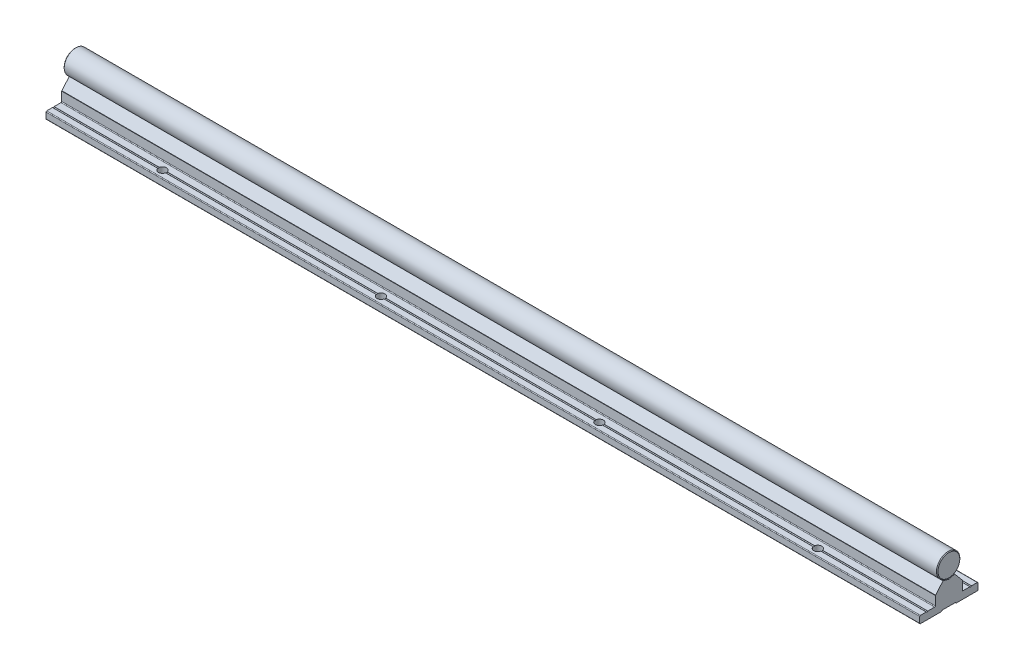
SolidWorks part; units mm, degrees
note: The reader was unsure of these and kept them because the rebuilt part matched: shared geometry of "Эскиз1<3>".
ref_plane "Спереди" through (0, 0, 0) normal (0, 0, 1) x (1, 0, 0)
ref_plane "Сверху" through (0, 0, 0) normal (0, 1, 0) x (1, 0, 0)
ref_plane "Справа" through (0, 0, 0) normal (1, 0, 0) x (0, 0, -1)
sketch "Эскиз1" plane through (0, 0, 0) normal (1, 0, 0) x (0, 0, -1)
  line L0 (0, 0) -> (0, -25) construction
  line L1 (0, -25) -> (-20, -25) construction
  line L2 (-4.75, -25) -> (-20, -25)
  line L3 (-20, -25) -> (-20, -20)
  line L4 (-20, -20) -> (-9.25, -20)
  line L5 (-9.25, -20) -> (-9.25, -13.3)
  line L6 (-9.25, -13.3) -> (-9.1101, -13.3)
  line L7 (-9.1101, -13.3) -> (-4, -7.21)
  line L8 (-4, -7.21) -> (-3.8, -7.21)
  line L9 (-3.8, -7.21) -> (0, -8.3557)
  line L10 (-2.75, -7.5266) -> (-2.75, -19) construction
  line L11 (-2.75, -19) -> (-4.75, -19) construction
  line L12 (-4.75, -19) -> (-4.75, -25) construction
  line L13 (-4.75, -25) -> (-4.75, -24.4)
  line L14 (-4.75, -24.4) -> (4.75, -24.4)
  line L15 (4.75, -25) -> (4.75, -24.4)
  line L16 (4.75, -25) -> (20, -25)
  line L17 (20, -25) -> (20, -20)
  line L18 (20, -20) -> (9.25, -20)
  line L19 (9.25, -20) -> (9.25, -13.3)
  line L20 (9.25, -13.3) -> (9.1101, -13.3)
  line L21 (9.1101, -13.3) -> (4, -7.21)
  line L22 (4, -7.21) -> (3.8, -7.21)
  line L23 (3.8, -7.21) -> (0, -8.3557)
  line L24 (-15, -20) -> (-15, -25) construction
  line L25 (-15.5, -20) -> (-15, -20.5)
  line L26 (-15, -20.5) -> (-14.5, -20)
  line L27 (15.5, -20) -> (15, -20.5)
  line L28 (15, -20) -> (15, -25) construction
  line L29 (15, -20.5) -> (14.5, -20)
  circle A0 centre (0, 0) radius 8
  point P17 (0, -24.4)
  dimension "D1" = 16
  dimension "D2" = 17.79
  dimension "D3" = 8
  dimension "D4" = 40
  dimension "D5" = 0.2
  dimension "D6" = 18.5
  dimension "D7" = 5
  dimension "D8" = 40
  dimension "D9" = 11.7
  dimension "D10" = 4.75
  dimension "D11" = 2.75
  dimension "D12" = 6
  dimension "D13" = 0.6
  dimension "D14" = 1
  dimension "D15" = 15
  dimension "D16" = 25
extrude "Опора" add sketch "Эскиз1" along normal mid plane 3000 contours L27 L29 L18 L19 L20 L21 L22 L23 L9 L8 L7 L6 L5 L4 L26 L25 L3 L2 L13 L14 L15 L16 L17
extrude "Вал" add sketch "Эскиз1<3>" along normal mid plane 3000 separate body contours A0
sketch "Эскиз1<3>" plane through (0, 0, 0) normal (1, 0, 0) x (0, 0, -1) same geometry as "Эскиз1"
fillet "Скругление4" radius 0.2 7 edges at (0, -20, -15.5) (0, -20, -14.5) (0, -20, 14.5) (0, -20, 15.5) (0, -8.3557, 0) (0, -24.4, -4.75) (0, -24.4, 4.75)
sketch "Эскиз2" plane through (0, -20, 0) normal (0, 1, 0) x (1, 0, 0)
  line L0 (-1425, 15) -> (-1425, -15) construction
  line L1 (1500, 15) -> (-1500, 15) construction
  line L2 (1500, -15) -> (-1500, -15) construction
  line L3 (-1500, 8) -> (-1500, -8) construction
  line L4 (-1275, 15) -> (-1275, -15) construction
  line L5 (-1125, 15) -> (-1125, -15) construction
  line L6 (-975, 15) -> (-975, -15) construction
  line L7 (-825, 15) -> (-825, -15) construction
  line L8 (-675, 15) -> (-675, -15) construction
  line L9 (-525, 15) -> (-525, -15) construction
  line L10 (-375, 15) -> (-375, -15) construction
  line L11 (-225, 15) -> (-225, -15) construction
  line L12 (-75, 15) -> (-75, -15) construction
  line L13 (75, 15) -> (75, -15) construction
  line L14 (225, 15) -> (225, -15) construction
  line L15 (375, 15) -> (375, -15) construction
  line L16 (525, 15) -> (525, -15) construction
  line L17 (675, 15) -> (675, -15) construction
  line L18 (825, 15) -> (825, -15) construction
  line L19 (975, 15) -> (975, -15) construction
  line L20 (1125, 15) -> (1125, -15) construction
  line L21 (1275, 15) -> (1275, -15) construction
  line L22 (1425, 15) -> (1425, -15) construction
  circle A0 centre (-1425, -15) radius 2.75
  circle A1 centre (-1425, 15) radius 2.75
  circle A2 centre (-1275, -15) radius 2.75
  circle A3 centre (-1275, 15) radius 2.75
  circle A4 centre (-1125, -15) radius 2.75
  circle A5 centre (-1125, 15) radius 2.75
  circle A6 centre (-975, -15) radius 2.75
  circle A7 centre (-975, 15) radius 2.75
  circle A8 centre (-825, -15) radius 2.75
  circle A9 centre (-825, 15) radius 2.75
  circle A10 centre (-675, -15) radius 2.75
  circle A11 centre (-675, 15) radius 2.75
  circle A12 centre (-525, -15) radius 2.75
  circle A13 centre (-525, 15) radius 2.75
  circle A14 centre (-375, -15) radius 2.75
  circle A15 centre (-375, 15) radius 2.75
  circle A16 centre (-225, -15) radius 2.75
  circle A17 centre (-225, 15) radius 2.75
  circle A18 centre (-75, -15) radius 2.75
  circle A19 centre (-75, 15) radius 2.75
  circle A20 centre (75, -15) radius 2.75
  circle A21 centre (75, 15) radius 2.75
  circle A22 centre (225, -15) radius 2.75
  circle A23 centre (225, 15) radius 2.75
  circle A24 centre (375, -15) radius 2.75
  circle A25 centre (375, 15) radius 2.75
  circle A26 centre (525, -15) radius 2.75
  circle A27 centre (525, 15) radius 2.75
  circle A28 centre (675, -15) radius 2.75
  circle A29 centre (675, 15) radius 2.75
  circle A30 centre (825, -15) radius 2.75
  circle A31 centre (825, 15) radius 2.75
  circle A32 centre (975, -15) radius 2.75
  circle A33 centre (975, 15) radius 2.75
  circle A34 centre (1125, -15) radius 2.75
  circle A35 centre (1125, 15) radius 2.75
  circle A36 centre (1275, -15) radius 2.75
  circle A37 centre (1275, 15) radius 2.75
  circle A38 centre (1425, -15) radius 2.75
  circle A39 centre (1425, 15) radius 2.75
  dimension "D1" = 5.5
  dimension "D2" = 5.5
  dimension "D6" = 5.5
  dimension "D7" = 5.5
  dimension "D3" = 75
  dimension "D5" = 150
  dimension "D4" = 20
extrude "Вырез-Вытянуть1" cut sketch "Эскиз2" against normal through all
sketch "Эскиз3" plane through (0, 0, 0) normal (0, 0, 1) x (1, 0, 0)
  line L0 (-1425, 56.4349) -> (-1425, -59.6123) construction
  line L1 (-1500, 8) -> (-1500, -8) construction
  line L2 (-1500, 0) -> (-1425, 0) construction
  line L3 (-1425, 0) -> (-1427.2, -1.2702)
  line L4 (-1427.2, -1.2702) -> (-1427.2, -7.5)
  line L5 (-1427.2, -7.5) -> (-1427.75, -7.5)
  line L6 (-1427.75, -7.5) -> (-1427.75, -19)
  line L7 (-1427.75, -19) -> (-1429.75, -19)
  line L8 (-1429.75, -19) -> (-1429.75, -24.4)
  line L9 (1500, -24.4) -> (-1500, -24.4) construction
  line L10 (-1429.75, -24.4) -> (-1425, -24.4)
  line L11 (-1425, -24.4) -> (-1425, 0)
  line L12 (1500, -25) -> (-1500, -25) construction
  point P20 (-1428.75, -19)
  dimension "D1" = 75
  dimension "D2" = 9.5
  dimension "D3" = 60
  dimension "D4" = 6
  dimension "D5" = 2.75
  dimension "D6" = 7.5
  dimension "D7" = 4.4
revolve "Вырез-Повернуть1" cut sketch "Эскиз3" angle 360 about L0
pattern_linear "Линейный массив1" count 20 spacing 150 along (1, 0, 0) of "Вырез-Повернуть1"
sketch "Эскиз4" plane through (0, 0, 0) normal (0, 0, 1) x (1, 0, 0)
  line L0 (-1425, 39.8402) -> (-1425, -50.2749) construction
  line L1 (-1500, 8) -> (-1500, -8) construction
  line L2 (-1500, 0) -> (-1425, 0) construction
  line L3 (-1425, -10) -> (-1427.2, -10)
  line L4 (-1427.2, -10) -> (-1427.2, -1.2702)
  line L5 (-1427.2, -1.2702) -> (-1425, 0)
  line L6 (-1425, 0) -> (-1425, -10)
  dimension "D1" = 75
  dimension "D2" = 60
  dimension "D3" = 2.2
  dimension "D4" = 10
revolve "Вырез-Повернуть2" cut sketch "Эскиз4" angle 360 about L0
pattern_linear "Линейный массив2" count 20 spacing 150 along (1, 0, 0) of "Вырез-Повернуть2"
sketch "Эскиз5" plane through (0, 0, 0) normal (0, 0, 1) x (1, 0, 0)
  line L0 (-1425, 35.5296) -> (-1425, -41.3293) construction
  line L1 (-1500, 8) -> (-1500, -8) construction
  line L2 (-1425, -24) -> (-1429.5, -24)
  line L3 (-1429.5, -24) -> (-1429.5, -19)
  line L4 (-1429.75, -19) -> (-1420.25, -19) construction
  line L5 (-1429.5, -19) -> (-1427.5, -19)
  line L6 (-1427.5, -19) -> (-1427.5, -2.4619)
  line L7 (-1427.5, -2.4619) -> (-1426.7, -2)
  line L8 (-1426.7, -2) -> (-1425, -2)
  line L9 (-1425, -2) -> (-1425, -24)
  dimension "D1" = 75
  dimension "D2" = 0.8
  dimension "D3" = 30
  dimension "D4" = 5
  dimension "D5" = 17
  dimension "D6" = 5
  dimension "D7" = 9
revolve "Повернуть1" add sketch "Эскиз5" angle 360 about L0
fillet "Скругление1" radius 0.3 1 edges at (-1425, -19, 4.5)
sketch "Эскиз6" plane through (0, -24, 0) normal (0, -1, 0) x (1, 0, 0)
  line L1 (-1423.25, -1.0104) -> (-1423.25, 1.0104)
  line L2 (-1423.25, 1.0104) -> (-1425, 2.0207)
  line L3 (-1425, 2.0207) -> (-1426.75, 1.0104)
  line L4 (-1426.75, 1.0104) -> (-1426.75, -1.0104)
  line L5 (-1426.75, -1.0104) -> (-1425, -2.0207)
  line L6 (-1425, -2.0207) -> (-1423.25, -1.0104)
  circle A0 centre (-1425, 0) radius 1.75 construction
  dimension "D1" = 3.5
extrude "Вырез-Вытянуть2" cut sketch "Эскиз6" against normal blind 3
fillet "Скругление2" radius 0.3 7 edges at (-1425, -24, 4.5) (-1423.25, -24, 0) (-1424.125, -24, 1.5155) (-1425.875, -24, 1.5155) (-1426.75, -24, 0) (-1425.875, -24, -1.5155) (-1424.125, -24, -1.5155)
pattern_linear "Линейный массив3" count 20 spacing 150 along (1, 0, 0) of bodies 114
chamfer "Фаска1" distance 0.5 angle 45 2 edges at (1500, 0, -8) (-1500, 0, -8)
fillet "Скругление3" radius 0.5 8 edges at (0, -20, -9.25) (0, -20, -20) (0, -25, -20) (0, -25, -4.75) (0, -25, 4.75) (0, -20, 9.25) (0, -25, 20) (0, -20, 20)
fillet "Скругление5" radius 0.2 4 edges at (0, -7.21, -3.8) (0, -7.21, -4) (0, -7.21, 4) (0, -7.21, 3.8)
fillet "Скругление6" radius 0.1 2 edges at (0, -13.3, -9.25) (0, -13.3, 9.25)
fillet "Скругление7" radius 0.1 2 edges at (0, -13.3, 9.1101) (0, -13.3, -9.1101)
sketch "Эскиз7" plane through (0, 0, 0) normal (0, 1, 0) x (1, 0, 0)
  line L1 (-300, 500) -> (300, 500)
  line L2 (-300, 500) -> (-300, -500)
  line L3 (-300, -500) -> (300, -500)
  line L4 (300, 500) -> (300, -500)
  line L5 (-300, 500) -> (300, -500) construction
  line L6 (-300, -500) -> (300, 500) construction
  line L7 (-1750, 750) -> (1750, 750)
  line L8 (-1750, 750) -> (-1750, -750)
  line L9 (-1750, -750) -> (1750, -750)
  line L10 (1750, 750) -> (1750, -750)
  line L11 (-1750, 750) -> (1750, -750) construction
  line L12 (-1750, -750) -> (1750, 750) construction
  point P0 (0, 0)
  point P6 (0, 0)
  dimension "D1" = 3500
  dimension "D2" = 600
  dimension "D3" = 1000
  dimension "D4" = 1500
extrude "Вырез-Вытянуть3" cut sketch "Эскиз7" against normal through all both and the other way through all
chamfer "Фаска2" distance 0.5 angle 45 2 edges at (300, 0, -8) (-300, 0, 8)
